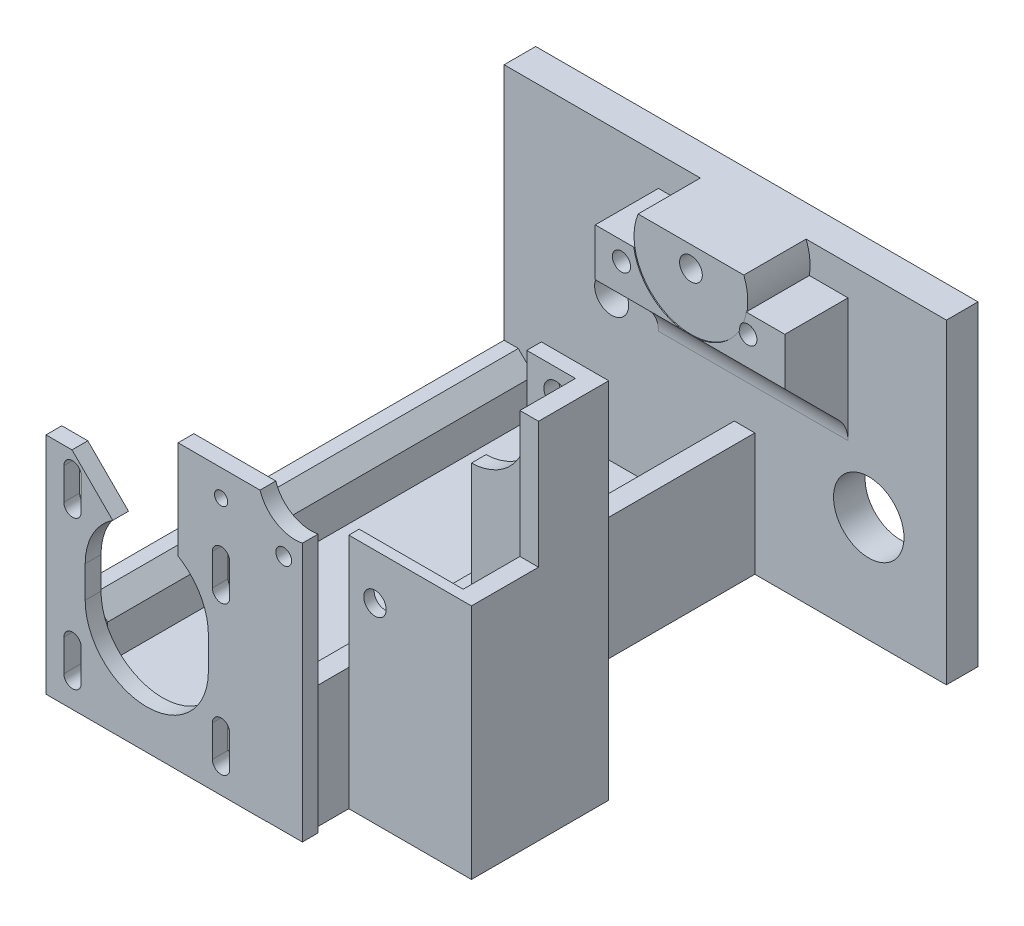
SolidWorks part; units mm, degrees
material "ABS"
ref_plane "Front Plane" through (0, 0, 0) normal (0, 0, 1) x (1, 0, 0)
ref_plane "Top Plane" through (0, 0, 0) normal (0, 1, 0) x (1, 0, 0)
ref_plane "Right Plane" through (0, 0, 0) normal (1, 0, 0) x (0, 0, -1)
sketch "Sketch1" plane through (0, 0, 0) normal (0, 0, 1) x (1, 0, 0)
  line L1 (-65.5446, 32.6733) -> (74.4554, 32.6733)
  line L2 (-65.5446, 32.6733) -> (-65.5446, -67.3267)
  line L3 (-65.5446, -67.3267) -> (74.4554, -67.3267)
  line L4 (74.4554, 32.6733) -> (74.4554, -67.3267)
  dimension "D1" = 100
  dimension "D2" = 140
extrude "Boss-Extrude1" add sketch "Sketch1" along normal blind 10
sketch "Sketch2" plane through (0, 0, 10) normal (0, 0, 1) x (1, 0, 0)
  line L0 (-65.5446, -67.3267) -> (-65.5446, -42.849)
  line L3 (-65.5446, -67.3267) -> (7.3151, -67.3267)
  line L5 (-65.5446, -67.3267) -> (74.4554, -67.3267) construction
  line L8 (-65.5446, 32.6733) -> (-65.5446, -67.3267) construction
  line L9 (-65.5446, -42.849) -> (-56.0483, -42.849)
  line L10 (-56.0483, -42.849) -> (-56.0483, -59.0904)
  line L11 (-56.0483, -59.0904) -> (7.3151, -59.0904)
  line L12 (7.3151, -59.0904) -> (7.3151, -28.5708)
  line L13 (7.3151, -28.5708) -> (13.8255, -28.5708)
  line L14 (13.8255, -28.5708) -> (13.8255, -67.3267)
  line L15 (13.8255, -67.3267) -> (7.3151, -67.3267)
extrude "Boss-Extrude2" add sketch "Sketch2" along normal blind 140
sketch "Sketch3" plane through (0, 0, 10) normal (0, 0, 1) x (1, 0, 0)
  line L1 (-16.6941, 23.1955) -> (43.3059, 23.1955)
  line L2 (-16.6941, 23.1955) -> (-16.6941, 8.1955)
  line L3 (-16.6941, 8.1955) -> (43.3059, 8.1955)
  line L4 (43.3059, 23.1955) -> (43.3059, 8.1955)
  dimension "D1" = 15
  dimension "D2" = 60
extrude "Boss-Extrude3" add sketch "Sketch3" along normal blind 20
sketch "Sketch4" plane through (0, 0, 10) normal (0, 0, 1) x (1, 0, 0)
  line L0 (43.3059, 8.1955) -> (43.3059, 23.1955) construction
  circle A0 centre (13.3059, 26.0432) radius 18
  dimension "D1" = 36
  dimension "D2" = 30
extrude "Boss-Extrude4" add sketch "Sketch4" along normal blind 20
sketch "Sketch6" plane through (0, 0, 30) normal (0, 0, 1) x (1, 0, 0)
  circle A0 centre (13.3059, 26.0432) radius 3.5973
  arc A1 (31.0792, 23.1955) -> (-4.4674, 23.1955) centre (13.3059, 26.0432) ccw construction
extrude "Cut-Extrude2" cut sketch "Sketch6" against normal blind 100
sketch "Sketch5" plane through (0, 0, 30) normal (0, 0, 1) x (1, 0, 0)
  line L0 (74.4554, 32.6733) -> (30.0404, 32.6733) construction
  line L1 (-13.303, 47.4) -> (34.4273, 47.4)
  line L2 (-13.303, 47.4) -> (-13.303, 32.6733)
  line L3 (-13.303, 32.6733) -> (34.4273, 32.6733)
  line L4 (34.4273, 47.4) -> (34.4273, 32.6733)
extrude "Cut-Extrude1" cut sketch "Sketch5" against normal blind 20
sketch "Sketch7" plane through (0, 0, 30) normal (0, 0, 1) x (1, 0, 0)
  circle A0 centre (-8.3949, 17.2978) radius 2.8779
extrude "Cut-Extrude3" cut sketch "Sketch7" against normal blind 100
pattern_linear "LPattern1" count 2 spacing 40 along (1, 0, 0) of "Cut-Extrude3"
sketch "Sketch9" plane through (0, 0, 150) normal (0, 0, 1) x (1, 0, 0)
  line L0 (-65.5446, 32.6733) -> (-65.5446, -42.849) construction
  line L1 (4.1877, 3.7072) -> (-65.5446, 3.7072)
  line L2 (4.1877, 3.7072) -> (4.1877, -67.3896)
  line L3 (4.1877, -67.3896) -> (-65.5446, -67.3896)
  line L4 (-65.5446, 3.7072) -> (-65.5446, -67.3896)
extrude "Boss-Extrude5" add sketch "Sketch9" along normal blind 5
chamfer "Chamfer1" distance 20 angle 45 2 edges at (29.4741, 8.1955, 10) (-2.8623, 8.1955, 10)
sketch "Sketch10" plane through (0, 0, 155) normal (0, 0, 1) x (1, 0, 0)
  line L1 (-37.3082, 6.7363) -> (-23.6547, 6.7363)
  line L2 (-37.3082, 6.7363) -> (-37.3082, -38.0615)
  line L3 (-37.3082, -38.0615) -> (-23.6547, -38.0615)
  line L4 (-23.6547, 6.7363) -> (-23.6547, -38.0615)
extrude "Cut-Extrude4" cut sketch "Sketch10" against normal blind 10
sketch "Sketch11" plane through (0, 0, 155) normal (0, 0, 1) x (1, 0, 0)
  line L0 (13.8255, -67.3267) -> (74.4554, -67.3267) construction
  line L1 (-23.7439, 22.4423) -> (15.6103, 22.4423)
  line L2 (-23.7439, 22.4423) -> (-23.7439, -67.3267)
  line L3 (-23.7439, -67.3267) -> (15.6103, -67.3267)
  line L4 (15.6103, 22.4423) -> (15.6103, -67.3267)
extrude "Boss-Extrude6" add sketch "Sketch11" against normal blind 5
sketch "Sketch12" plane through (0, 0, 155) normal (0, 0, 1) x (1, 0, 0)
  circle A0 centre (13.3059, 26.0432) radius 11.6785
extrude "Cut-Extrude5" cut sketch "Sketch12" against normal blind 10
sketch "Sketch13" plane through (0, 0, 155) normal (0, 0, 1) x (1, 0, 0)
  circle A0 centre (-10.1053, 14.0773) radius 2.089
  circle A1 centre (9.687, 8.0077) radius 2.4987
extrude "Cut-Extrude6" cut sketch "Sketch13" against normal blind 10
fillet "Fillet2" radius 10 1 edges at (13.3059, -11.8045, 10)
chamfer "Chamfer2" distance 5 angle 45 1 edges at (-56.0483, -42.849, 80)
sketch "Sketch14" plane through (0, 0, 10) normal (0, 0, 1) x (1, 0, 0)
  circle A0 centre (-31.5077, -13.6101) radius 5.3914
  circle A1 centre (49.8779, -33.6888) radius 11.1548
extrude "Cut-Extrude7" cut sketch "Sketch14" against normal blind 10
chamfer "Chamfer3" distance 20 angle 45 1 edges at (-37.3082, 3.7072, 152.5)
sketch "Sketch15" plane through (0, -67.3267, 0) normal (0, -1, 0) x (1, 0, 0)
  line L1 (4.5956, 95.0738) -> (52.6384, 95.0738)
  line L2 (4.5956, 95.0738) -> (4.5956, 138.5253)
  line L3 (4.5956, 138.5253) -> (52.6384, 138.5253)
  line L4 (52.6384, 95.0738) -> (52.6384, 138.5253)
extrude "Boss-Extrude7" add sketch "Sketch15" against normal blind 5
sketch "Sketch16" plane through (0, -62.3267, 0) normal (0, 1, 0) x (1, 0, 0)
  line L8 (13.8255, -135.2423) -> (13.8255, -138.5253)
  line L9 (13.8255, -138.5253) -> (13.8255, -95.0738) construction
  line L10 (13.8255, -138.5253) -> (52.6384, -138.5253)
  line L11 (52.6384, -138.5253) -> (52.6384, -116.7995)
  line L12 (52.6384, -95.0738) -> (52.6384, -138.5253) construction
  line L13 (52.6384, -116.7995) -> (46.7483, -116.7995)
  line L14 (46.7483, -116.7995) -> (46.7483, -135.2423)
  line L15 (46.7483, -135.2423) -> (13.8255, -135.2423)
extrude "Boss-Extrude8" add sketch "Sketch16" along normal blind 70
sketch "Sketch17" plane through (0, 7.6733, 0) normal (0, 1, 0) x (1, 0, 0)
  line L1 (28.8586, -179.0031) -> (38.4745, -179.0031)
  line L2 (28.8586, -179.0031) -> (28.8586, -197.9959)
  line L3 (28.8586, -197.9959) -> (38.4745, -197.9959)
  line L4 (38.4745, -179.0031) -> (38.4745, -197.9959)
extrude "Cut-Extrude8" cut sketch "Sketch17" against normal blind 20 rebuild error yes
sketch "Sketch18" plane through (0, 0, 138.5253) normal (0, 0, 1) x (1, 0, 0)
  circle A0 centre (22.1124, -6.8448) radius 3.5565
extrude "Cut-Extrude9" cut sketch "Sketch18" against normal blind 20
sketch "Sketch19" plane through (0, -62.3267, 0) normal (0, 1, 0) x (1, 0, 0)
  line L0 (13.8199, -95.0738) -> (13.8199, -99.7086)
  line L3 (13.8199, -99.7086) -> (46.7483, -99.7086)
  line L6 (46.7483, -99.7086) -> (46.7483, -117.2823)
  line L7 (46.7483, -117.2823) -> (52.6384, -117.2823)
  line L8 (52.6384, -95.0738) -> (52.6384, -116.7995) construction
  line L9 (52.6384, -117.2823) -> (52.6384, -95.0738)
  line L10 (52.6384, -95.0738) -> (13.8199, -95.0738)
extrude "Boss-Extrude9" add sketch "Sketch19" along normal blind 110
sketch "Sketch20" plane through (0, 0, 99.7086) normal (0, 0, 1) x (1, 0, 0)
  line L0 (13.3059, 26.0432) -> (13.3059, 51.1413) construction
  line L1 (-4.7235, 26.0432) -> (-4.7235, 51.1413)
  line L2 (31.3354, 26.0432) -> (31.3354, 51.1413)
  arc A0 (-4.7235, 26.0432) -> (31.3354, 26.0432) centre (13.3059, 26.0432) ccw
  arc A1 (31.3354, 51.1413) -> (-4.7235, 51.1413) centre (13.3059, 51.1413) ccw
  point P3 (13.3059, 38.5923)
extrude "Cut-Extrude10" cut sketch "Sketch20" against normal blind 70
sketch "Sketch21" plane through (0, 0, 99.7086) normal (0, 0, 1) x (1, 0, 0)
  circle A0 centre (40.582, 40.031) radius 3.8105
extrude "Cut-Extrude11" cut sketch "Sketch21" against normal blind 70
sketch "Sketch22" plane through (0, 0, 155) normal (0, 0, 1) x (1, 0, 0)
  line L0 (-57.1445, -58.9171) -> (-57.1445, -48.9171) construction
  line L1 (-59.8916, -58.9171) -> (-59.8916, -48.9171)
  line L2 (-54.3974, -58.9171) -> (-54.3974, -48.9171)
  line L3 (-33.6445, -35.4171) -> (-33.6445, -25.4171) construction
  line L4 (-53.1445, -35.4171) -> (-53.1445, -25.4171)
  line L5 (-14.1445, -35.4171) -> (-14.1445, -25.4171)
  line L6 (-10.1445, -58.9171) -> (-10.1445, -48.9171) construction
  line L7 (-12.8916, -58.9171) -> (-12.8916, -48.9171)
  line L8 (-7.3974, -58.9171) -> (-7.3974, -48.9171)
  line L9 (-10.1445, -11.9171) -> (-10.1445, -1.9171) construction
  line L10 (-12.8916, -11.9171) -> (-12.8916, -1.9171)
  line L11 (-7.3974, -11.9171) -> (-7.3974, -1.9171)
  line L12 (-57.1445, -11.9171) -> (-57.1445, -1.9171) construction
  line L13 (-59.8916, -11.9171) -> (-59.8916, -1.9171)
  line L14 (-54.3974, -11.9171) -> (-54.3974, -1.9171)
  arc A0 (-59.8916, -58.9171) -> (-54.3974, -58.9171) centre (-57.1445, -58.9171) ccw
  arc A1 (-54.3974, -48.9171) -> (-59.8916, -48.9171) centre (-57.1445, -48.9171) ccw
  arc A2 (-53.1445, -35.4171) -> (-14.1445, -35.4171) centre (-33.6445, -35.4171) ccw
  arc A3 (-14.1445, -25.4171) -> (-53.1445, -25.4171) centre (-33.6445, -25.4171) ccw
  arc A4 (-12.8916, -58.9171) -> (-7.3974, -58.9171) centre (-10.1445, -58.9171) ccw
  arc A5 (-7.3974, -48.9171) -> (-12.8916, -48.9171) centre (-10.1445, -48.9171) ccw
  arc A6 (-12.8916, -11.9171) -> (-7.3974, -11.9171) centre (-10.1445, -11.9171) ccw
  arc A7 (-7.3974, -1.9171) -> (-12.8916, -1.9171) centre (-10.1445, -1.9171) ccw
  arc A8 (-59.8916, -11.9171) -> (-54.3974, -11.9171) centre (-57.1445, -11.9171) ccw
  arc A9 (-54.3974, -1.9171) -> (-59.8916, -1.9171) centre (-57.1445, -1.9171) ccw
  point P2 (-57.1445, -53.9171)
  point P9 (-33.6445, -30.4171)
  point P16 (-10.1445, -53.9171)
  point P23 (-10.1445, -6.9171)
  point P30 (-57.1445, -6.9171)
  dimension "D5" = 19.5
  dimension "D1" = 10
  dimension "D2" = 10
  dimension "D3" = 23.5
  dimension "D4" = 23.5
extrude "Cut-Extrude12" cut sketch "Sketch22" against normal blind 10
